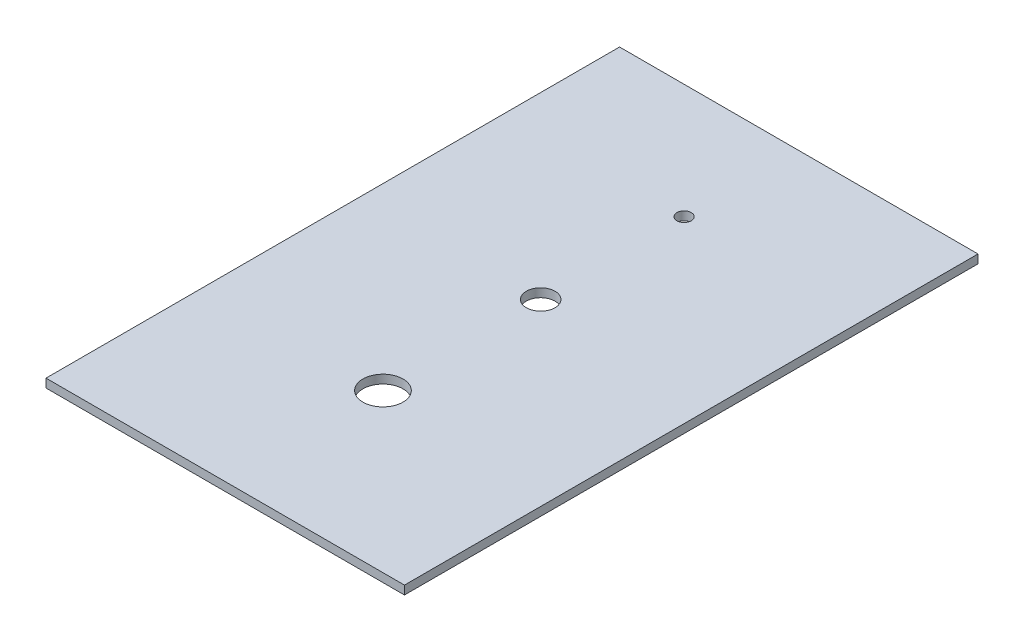
SolidWorks part; units mm, degrees
ref_plane "Front Plane" through (0, 0, 0) normal (0, 0, 1) x (1, 0, 0)
ref_plane "Top Plane" through (0, 0, 0) normal (0, 1, 0) x (1, 0, 0)
ref_plane "Right Plane" through (0, 0, 0) normal (1, 0, 0) x (0, 0, -1)
sketch "Sketch1" plane through (0, 0, 0) normal (0, 1, 0) x (1, 0, 0)
  line L1 (-62.5, -100) -> (62.5, -100)
  line L2 (-62.5, -100) -> (-62.5, 100)
  line L3 (-62.5, 100) -> (62.5, 100)
  line L4 (62.5, -100) -> (62.5, 100)
  line L5 (-62.5, -100) -> (62.5, 100) construction
  line L6 (-62.5, 100) -> (62.5, -100) construction
  point P0 (0, 0)
  dimension "D1" = 125
  dimension "D2" = 200
extrude "Boss-Extrude1" add sketch "Sketch1" along normal blind 3
sketch "Sketch2" plane through (0, 3, 0) normal (0, 1, 0) x (1, 0, 0)
  line L0 (0, 100) -> (0, -100) construction
  line L1 (62.5, 100) -> (-62.5, 100) construction
  line L2 (-62.5, -100) -> (62.5, -100) construction
  circle A0 centre (0, 60) radius 2.5
  circle A1 centre (0, -45) radius 7
  circle A2 centre (0, 10) radius 5
  dimension "D1" = 5
  dimension "D2" = 10
  dimension "D3" = 14
  dimension "D4" = 40
  dimension "D5" = 90
  dimension "D6" = 145
extrude "Cut-Extrude1" cut sketch "Sketch2" along direction (0, -1, 0) on the side against the normal up to next (3 mm away)
